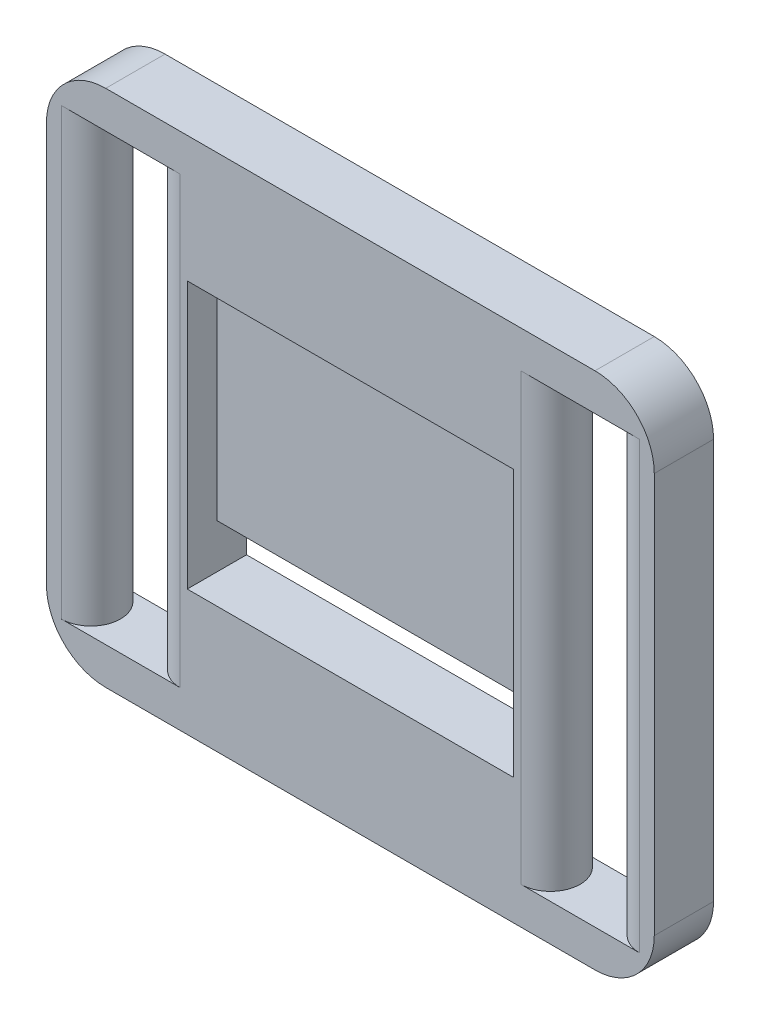
SolidWorks part; units mm, degrees
ref_plane "Plan de face" through (0, 0, 0) normal (0, 0, 1) x (1, 0, 0)
ref_plane "Plan de dessus" through (0, 0, 0) normal (0, 1, 0) x (1, 0, 0)
ref_plane "Plan de droite" through (0, 0, 0) normal (1, 0, 0) x (0, 0, -1)
sketch "Esquisse1" plane through (0, 0, 0) normal (0, 0, 1) x (1, 0, 0)
  line L1 (0, 0) -> (41, 0)
  line L2 (0, 0) -> (0, 35)
  line L3 (0, 35) -> (41, 35)
  line L4 (41, 0) -> (41, 35)
  dimension "D1" = 41
  dimension "D2" = 35
extrude "Boss.-Extru.1" add sketch "Esquisse1" along normal blind 4
sketch "Esquisse2" plane through (0, 0, 4) normal (0, 0, 1) x (1, 0, 0)
  line L0 (0, 35) -> (0, 0) construction
  line L1 (9.5, 26.5) -> (31.5, 26.5)
  line L2 (9.5, 26.5) -> (9.5, 8.5)
  line L3 (9.5, 8.5) -> (31.5, 8.5)
  line L4 (31.5, 26.5) -> (31.5, 8.5)
  line L5 (0, 0) -> (41, 0) construction
  line L6 (20.5, 0) -> (20.5, 35) construction
  line L7 (41, 35) -> (0, 35) construction
  dimension "D1" = 22
  dimension "D2" = 18
  dimension "D3" = 9.5
  dimension "D4" = 8.5
extrude "Enlèv. mat.-Extru.1" cut sketch "Esquisse2" against normal blind 2
sketch "Esquisse3" plane through (0, 0, 4) normal (0, 0, 1) x (1, 0, 0)
  line L0 (0, 35) -> (0, 0) construction
  line L1 (3, 32.5) -> (7, 32.5)
  line L2 (3, 32.5) -> (3, 2.5)
  line L3 (3, 2.5) -> (7, 2.5)
  line L4 (7, 32.5) -> (7, 2.5)
  line L5 (41, 35) -> (0, 35) construction
  line L6 (0, 0) -> (41, 0) construction
  line L7 (20.5, 35) -> (20.5, 0) construction
  line L8 (38, 32.5) -> (34, 32.5)
  line L9 (38, 32.5) -> (38, 2.5)
  line L10 (38, 2.5) -> (34, 2.5)
  line L11 (34, 32.5) -> (34, 2.5)
  line L12 (9.5, 26.5) -> (9.5, 8.5) construction
  line L13 (9.5, 11.5) -> (31.5, 11.5)
  line L14 (9.5, 11.5) -> (9.5, 8.5)
  line L15 (9.5, 8.5) -> (31.5, 8.5)
  line L16 (31.5, 11.5) -> (31.5, 8.5)
  line L17 (31.5, 8.5) -> (31.5, 26.5) construction
  line L18 (9.5, 8.5) -> (31.5, 8.5) construction
  dimension "D1" = 4
  dimension "D2" = 30
  dimension "D3" = 3
  dimension "D4" = 2.5
  dimension "D5" = 3
  dimension "D6" = 0
  dimension "D7" = 0
  dimension "D8" = 0
extrude "Enlèv. mat.-Extru.2" cut sketch "Esquisse3" against normal blind 6
fillet "Congé4" radius 4 4 edges at (41, 0, 2) (41, 35, 2) (0, 35, 2) (0, 0, 2) tangent propagation no
fillet "Congé6" 2 edges at (38, 17.5, 4) (38, 17.5, 0) type full round first side face at (36, 17.5, 4) second side face at (20.5, 10, 0) middle face at (38, 17.5, 2)
fillet "Congé7" 2 edges at (3, 17.5, 4) (3, 17.5, 0) type full round first side face at (37, 17.5, 4) second side face at (20.5, 10, 0) middle face at (3, 17.5, 2)
fillet "Congé8" 2 edges at (34, 17.5, 4) (34, 17.5, 0) type full round first side face at (37, 17.5, 4) second side face at (20.5, 10, 0) middle face at (34, 17.5, 2)
fillet "Congé9" 2 edges at (7, 17.5, 4) (7, 17.5, 0) type full round first side face at (36, 17.5, 4) second side face at (20.5, 10, 0) middle face at (7, 17.5, 2)
